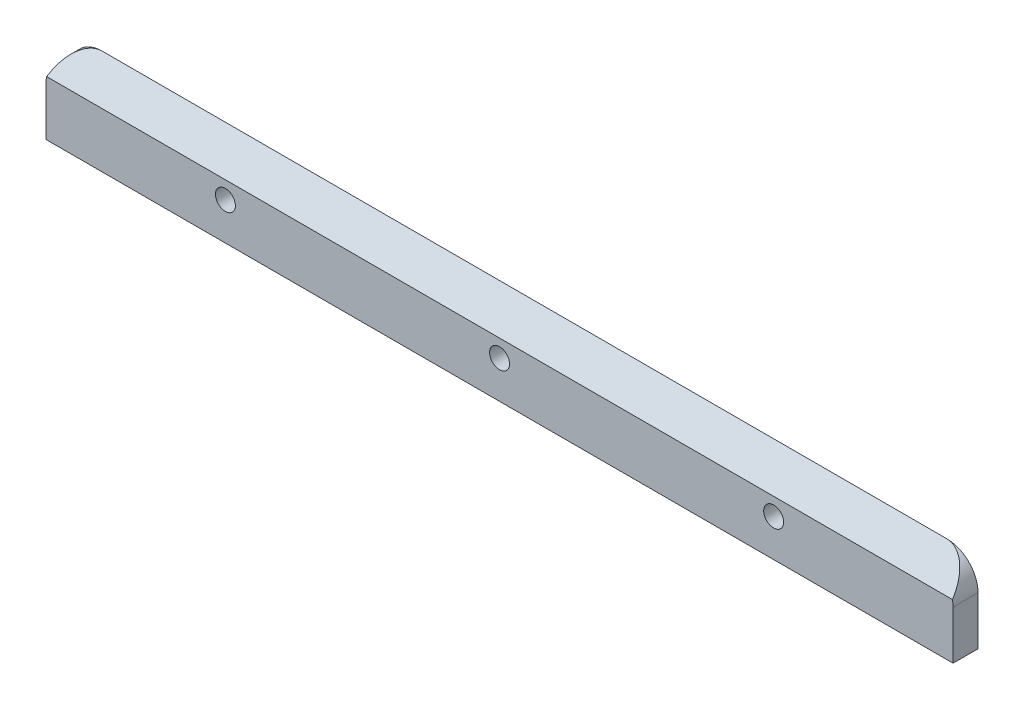
SolidWorks part; units mm, degrees
material "6061-T6 (SS)"
ref_plane "Front Plane" through (0, 0, 0) normal (0, 0, 1) x (1, 0, 0)
ref_plane "Top Plane" through (0, 0, 0) normal (0, 1, 0) x (1, 0, 0)
ref_plane "Right Plane" through (0, 0, 0) normal (1, 0, 0) x (0, 0, -1)
sketch "Sketch1" plane through (0, 0, 0) normal (1, 0, 0) x (0, 0, -1)
  line L0 (-3.0983, 0) -> (1.226, 0) construction
  line L2 (0, -3.2) -> (0, 3.2)
  line L4 (-2, -3.2) -> (-2, 3.2)
  line L5 (-2, 3.2) -> (0, 3.2)
  line L6 (0, -3.2) -> (-2, -3.2)
  dimension "D1" = 2
  dimension "D3" = 6.4
extrude "Boss-Extrude1" add sketch "Sketch1" along normal mid plane 72.8
fillet "Fillet3" radius 2.5 2 edges at (-36.4, 3.2, 1) (36.4, 3.2, 1)
sketch "Sketch5" [suppressed] plane through (-36.4, 0, 0) normal (-1, 0, 0) x (0, 0, 1)
  line L0 (0, -2.7) -> (2, -0.7)
  line L1 (0, -3.2) -> (0, 0.7) construction
  line L2 (2, 0.7) -> (2, -1.2) construction
  line L3 (2, -1.2) -> (0, -3.2) construction
  line L4 (2, -1.2) -> (2, -0.7)
  line L5 (2, -1.2) -> (0, -3.2)
  line L6 (0, -3.2) -> (0, -2.7)
  dimension "D1" = 0.5
extrude "Cut-Extrude5" [suppressed] cut sketch "Sketch5" against normal up to surface (72.8 mm away) up to face at (36.4, -1.25, 1)
sketch "Sketch7" [suppressed] plane through (-36.4, 0, 0) normal (-1, 0, 0) x (0, 0, 1)
  line L0 (0, -2.7) -> (-1, -1.7)
  line L1 (-1, -1.7) -> (-1, 3.2)
  line L2 (-1, 3.2) -> (0, 3.2)
  line L3 (0, 3.2) -> (0, -2.7)
  line L4 (0, 3.2) -> (2, 3.2) construction
  dimension "D1" = 45
  dimension "D2" = 3
extrude "Boss-Extrude2" [suppressed] add sketch "Sketch7" against normal up to surface (72.8 mm away) up to face at (36.4, -1.25, 1)
hole_wizard "M2x0.4 Tapped Hole1" positions "Sketch2" profile "Sketch3" tap size "M2x0.4" standard "ANSI Metric"
sketch "Sketch2" plane through (0, 0, 2) normal (0, 0, 1) x (1, 0, 0)
  circle A4 centre (-22, -0.2) radius 1.2 construction
  circle A5 centre (-22, -0.2) radius 1.2
  circle A8 centre (22, -0.2) radius 1.2 construction
  circle A9 centre (22, -0.2) radius 1.2
  circle A10 centre (0, -0.2) radius 1.2
  point P22 (-22, -0.2)
  point P28 (22, -0.2)
  point P31 (0, -0.2)
cosmetic thread "Hole Thread4" parameters "D1"=3, "D2"=2
cosmetic thread "Hole Thread6" parameters "D1"=3, "D2"=2
sketch "Sketch3" plane through (-22, -0.2, 2) normal (1, 0, 0) x (0, -1, 0)
  line L0 (0, 0) -> (0, 4.0807)
  line L1 (0, 4.0807) -> (0.8, 3.6)
  line L2 (0.8, 3.6) -> (0.8, 0)
  line L5 (0.8, 0) -> (0, 0)
  line L10 (0, 4.0807) -> (-0.8, 3.6) construction
  line L11 (0, -6.35) -> (0, 107.95) construction
  dimension "Tap Drill Dia." = 1.6
  dimension "Tap Drill Depth" = 3.6
  dimension "Drill Angle" = 118
cosmetic thread "Hole Thread7" [suppressed] parameters "D1"=3, "D2"=2
fillet "Fillet4" [suppressed] radius 2.5
sketch "Sketch4" [suppressed] plane through (0, 0, 0) normal (0, 0, 1) x (1, 0, 0)
  line L1 (7.5, 1.5) -> (-7.5, 1.5)
  line L2 (7.5, 1.5) -> (7.5, -3.2)
  line L3 (7.5, -3.2) -> (-7.5, -3.2)
  line L4 (-7.5, 1.5) -> (-7.5, -3.2)
  line L5 (0, 7.7759) -> (0, -8.8374) construction
  line L8 (-7.5, -1.7) -> (-7.5, -0.7) construction
  dimension "D1" = 4.7
extrude "Cut-Extrude4" [suppressed] cut sketch "Sketch4" along normal mid plane 10
sketch "Sketch8" [suppressed] plane through (36.4, 0, 0) normal (1, 0, 0) x (0, 0, -1)
  line L1 (-1, -3.2) -> (-2, -2.2)
  line L2 (-2, -2.2) -> (-2, -1.2)
  line L3 (-2, -1.2) -> (0, -3.2)
  line L4 (0, -3.2) -> (-1, -3.2)
  dimension "D1" = 1
extrude "Boss-Extrude3" [suppressed] add sketch "Sketch8" against normal blind 3
sketch "Sketch10" [suppressed] plane through (7.5, 0, 0) normal (-1, 0, 0) x (0, 0, 1)
  line L1 (1, -3.2) -> (2, -2.2)
  line L2 (2, -2.2) -> (2, -1.2)
  line L3 (2, -1.2) -> (0, -3.2)
  line L4 (2, -2.2) -> (1, -3.2) construction
  line L5 (0, -3.2) -> (1, -3.2)
extrude "Boss-Extrude5" [suppressed] add sketch "Sketch10" against normal blind 3
mirror "Mirror1" [suppressed] about plane through (0, 0, 0) normal (1, 0, 0)
sketch "Sketch11" [suppressed] plane through (36.4, 0, 0) normal (1, 0, 0) x (0, 0, -1)
  line L0 (0, -2.7) -> (-1, -2.7)
  line L1 (-1, -2.7) -> (-2, -1.7)
  line L2 (-2, -1.7) -> (-2, -0.7)
  line L3 (0, -2.7) -> (-2, -0.7)
  dimension "D1" = 1
extrude "Boss-Extrude6" [suppressed] add sketch "Sketch11" against normal blind 3
sketch "Sketch12" [suppressed] plane through (7.5, 0, 0) normal (-1, 0, 0) x (0, 0, 1)
  line L0 (0, -2.7) -> (1, -2.7)
  line L1 (1, -2.7) -> (2, -1.7)
  line L2 (2, -1.7) -> (2, -0.7)
  line L3 (0, -2.7) -> (2, -0.7)
  line L4 (1, -2.7) -> (0, -2.7) construction
  line L5 (2, -1.7) -> (1, -2.7) construction
extrude "Boss-Extrude7" [suppressed] add sketch "Sketch12" against normal blind 3
mirror "Mirror7" [suppressed] about plane through (0, 0, 0) normal (1, 0, 0) of bodies 112 111
sketch "Sketch13" [suppressed] plane through (0, 0, 2) normal (0, 0, 1) x (1, 0, 0)
  line L0 (24.4, 3.2) -> (24.4, -2.7)
  line L1 (33.9, 3.2) -> (-33.9, 3.2) construction
  line L2 (36.4, -2.7) -> (-36.4, -2.7) construction
  line L4 (24.4, -2.7) -> (36.4, -2.7)
  line L5 (36.4, -2.7) -> (36.4, 3.2)
  line L6 (36.4, 3.2) -> (24.4, 3.2)
  dimension "D1" = 12
extrude "Cut-Extrude6" [suppressed] cut sketch "Sketch13" against normal up to surface (3 mm away)
sketch "Sketch14" plane through (0, 0, 0) normal (1, 0, 0) x (0, 0, -1)
  line L0 (0, 3.2) -> (-2, 3.2)
  line L1 (-2, 3.2) -> (-2, 1.2)
  line L2 (-2, 3.2) -> (-2, 0.7) construction
  line L3 (-2, 1.2) -> (0, 3.2)
extrude "Cut-Extrude7" cut sketch "Sketch14" against normal through all both and the other way through all
